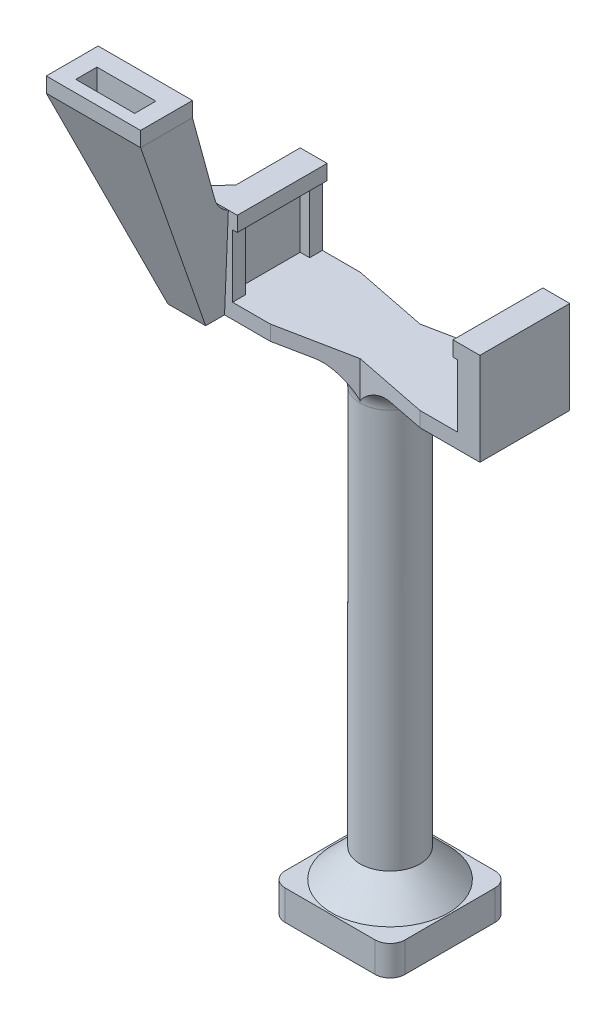
SolidWorks part; units mm, degrees
note: The reader was unsure of these and kept them because the rebuilt part matched: shared geometry of "Sketch3<2>".
ref_plane "Front Plane" through (0, 0, 0) normal (0, 0, 1) x (1, 0, 0)
ref_plane "Top Plane" through (0, 0, 0) normal (0, 1, 0) x (1, 0, 0)
ref_plane "Right Plane" through (0, 0, 0) normal (1, 0, 0) x (0, 0, -1)
sketch "Sketch1" plane through (0, 0, 0) normal (0, 1, 0) x (1, 0, 0)
  line L0 (12.7, 0) -> (28.575, 3.175)
  line L1 (0, 0) -> (12.7, 0)
  line L2 (0, 0) -> (0, 19.05)
  line L3 (0, 19.05) -> (12.7, 19.05)
  line L4 (57.15, 0) -> (57.15, 19.05)
  line L5 (28.575, 3.175) -> (44.45, 0)
  line L6 (44.45, 19.05) -> (57.15, 19.05)
  line L7 (44.45, 19.05) -> (28.575, 15.875)
  line L8 (28.575, 15.875) -> (12.7, 19.05)
  line L9 (44.45, 0) -> (57.15, 0)
  circle A0 centre (28.575, 9.525) radius 6.35 construction
  point P7 (28.575, 4.3732)
  point P12 (0, 0)
  dimension "D5" = 12.7
  dimension "D1" = 57.15
  dimension "D2" = 19.05
  dimension "D3" = 12.7
  dimension "D4" = 12.7
extrude "Boss-Extrude1" add sketch "Sketch1" along normal blind 3.175
sketch "Sketch2" plane through (0, 0, 0) normal (0, 0, 1) x (1, 0, 0)
  line L0 (0, 3.175) -> (0, 19.65)
  line L1 (0, 19.65) -> (5.7, 19.65)
  line L2 (5.7, 19.65) -> (5.7, 16.475)
  line L3 (5.7, 16.475) -> (2.7, 16.475)
  line L4 (2.7, 16.475) -> (2.7, 3.175)
  line L5 (0, 3.175) -> (12.7, 3.175) construction
  line L6 (28.575, 3.175) -> (28.575, 15.1808) construction
  line L7 (0, 3.175) -> (2.7, 3.175)
  line L8 (57.15, 3.175) -> (57.15, 19.65)
  line L9 (57.15, 19.65) -> (51.45, 19.65)
  line L10 (51.45, 19.65) -> (51.45, 16.475)
  line L11 (51.45, 16.475) -> (54.45, 16.475)
  line L12 (54.45, 16.475) -> (54.45, 3.175)
  line L13 (57.15, 3.175) -> (54.45, 3.175)
  dimension "D1" = 2.7
  dimension "D2" = 3.175
  dimension "D3" = 13.3
  dimension "D4" = 3
extrude "Boss-Extrude2" add sketch "Sketch2" against normal up to surface (19.05 mm away) up to face at (6.35, 1.5875, -19.05)
sketch "Sketch3" plane through (0, 0, 0) normal (0, 0, 1) x (1, 0, 0)
  line L0 (44.45, 3.175) -> (54.45, 3.175) construction
  line L1 (2.7, 16.475) -> (4.7, 16.475)
  line L2 (2.7, 16.475) -> (2.7, 3.175)
  line L3 (2.7, 3.175) -> (4.7, 3.175)
  line L4 (4.7, 16.475) -> (4.7, 3.175)
  line L5 (54.45, 16.475) -> (52.45, 16.475)
  line L6 (54.45, 16.475) -> (54.45, 3.175)
  line L7 (54.45, 3.175) -> (52.45, 3.175)
  line L8 (52.45, 16.475) -> (52.45, 3.175)
  line L9 (2.7, 3.175) -> (12.7, 3.175) construction
  dimension "D1" = 2
  dimension "D2" = 2
extrude "Boss-Extrude3" add sketch "Sketch3" against normal blind 2.7
extrude "Boss-Extrude4" add sketch "Sketch3<2>" along normal blind 2.7 from surface at -19.05 starting at face at (5.275, 9.825, -19.05)
sketch "Sketch3<2>" plane through (0, 0, 0) normal (0, 0, 1) x (1, 0, 0) same geometry as "Sketch3"
sketch "Sketch4" plane through (0, 0, 0) normal (0, -1, 0) x (1, 0, 0)
  circle A0 centre (28.575, -9.525) radius 6.35
  point P2 (0, 0)
extrude "Boss-Extrude5" add sketch "Sketch4" along normal blind 105.156 from surface at -3.175 starting at face at (28.575, 3.175, -9.525)
fillet "Fillet1" radius 5 2 edges at (22.225, 0, -9.525) (34.925, 0, -9.525)
ref_plane "Plane2" through (0, 41.305, 0) normal (0, 1, 0) x (1, 0, 0)
sketch "Sketch9" plane through (0, 41.305, 0) normal (0, 1, 0) x (1, 0, 0)
  line L0 (5.7, 0) -> (0, 0) construction
  line L1 (4.7, -8.5) -> (-15.3, -8.5)
  line L2 (4.7, -8.5) -> (4.7, -19.5)
  line L3 (4.7, -19.5) -> (-15.3, -19.5)
  line L4 (-15.3, -8.5) -> (-15.3, -19.5)
  dimension "D1" = 11
  dimension "D2" = 20
  dimension "D3" = 8.5
sketch "Sketch10" plane through (0, 0, 0) normal (0, -1, 0) x (1, 0, 0)
  line L0 (3, -4) -> (3, 4)
  line L2 (3, 4) -> (-5, 4)
  line L3 (-5, 4) -> (-5, -4)
  line L4 (-5, -4) -> (3, -4)
  line L7 (0, 0) -> (12.7, 0) construction
  point P2 (5.7731, -5.5033)
  point P3 (5.7731, -5.2557)
  point P4 (0, -6.3349)
  dimension "D1" = 8
  dimension "D2" = 8
  dimension "D3" = 5
  dimension "D4" = 4
loft "Loft2" add profiles "Sketch10", "Sketch9"
sketch "Sketch11" plane through (0, 41.305, 0) normal (0, 1, 0) x (1, 0, 0)
  line L1 (-15.3, -8.5) -> (4.7, -8.5)
  line L2 (-15.3, -8.5) -> (-15.3, -19.5)
  line L3 (-15.3, -19.5) -> (4.7, -19.5)
  line L4 (4.7, -8.5) -> (4.7, -19.5)
extrude "Boss-Extrude7" add sketch "Sketch11" along normal blind 3.175
fillet "Fillet3" radius 6 1 edges at (1.772, 13.2176, 0)
chamfer "Chamfer3" distance 7 angle 45 1 edges
sketch "Sketch12" plane through (0, 44.48, 0) normal (0, 1, 0) x (1, 0, 0)
  line L1 (-11.55, -12.5) -> (0.95, -12.5)
  line L2 (-11.55, -12.5) -> (-11.55, -17)
  line L3 (-11.55, -17) -> (0.95, -17)
  line L4 (0.95, -12.5) -> (0.95, -17)
  line L5 (-15.3, -19.5) -> (4.7, -19.5) construction
  point P4 (-5.3, -19.5)
  point P8 (-5.3, -17)
  dimension "D2" = 4.5
  dimension "D3" = 12.5
  dimension "D1" = 12.5
extrude "Cut-Extrude2" cut sketch "Sketch12" against normal blind 9
sketch "Sketch13" plane through (0, -101.981, 0) normal (0, -1, 0) x (1, 0, 0)
  line L1 (15.875, 3.175) -> (41.275, 3.175)
  line L2 (15.875, 3.175) -> (15.875, -22.225)
  line L3 (15.875, -22.225) -> (41.275, -22.225)
  line L4 (41.275, 3.175) -> (41.275, -22.225)
  circle A0 centre (28.575, -9.525) radius 6.35 construction
  circle A1 centre (28.575, -9.525) radius 6.35 construction
  point P7 (0, 0)
  point P8 (28.575, 3.175)
  point P9 (15.875, -9.525)
  dimension "D1" = 25.4
  dimension "D2" = 25.4
extrude "Boss-Extrude8" add sketch "Sketch13" against normal blind 6.35
chamfer "Chamfer4" distance 6 angle 45 1 edges at (28.575, -95.631, -15.875)
fillet "Fillet4" radius 3.175 4 edges at (15.875, -98.806, 3.175) (15.875, -98.806, -22.225) (41.275, -98.806, -22.225) (41.275, -98.806, 3.175)
